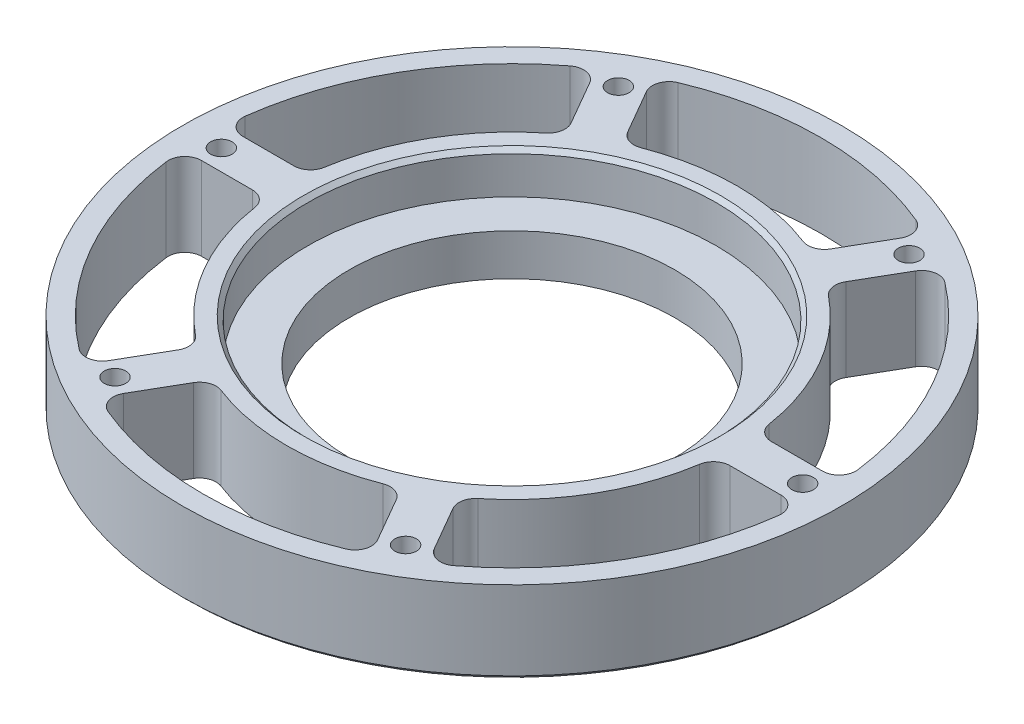
SolidWorks part; units mm, degrees
material "6061-T6 (SS)"
ref_plane "Front Plane" through (0, 0, 0) normal (0, 0, 1) x (1, 0, 0)
ref_plane "Top Plane" through (0, 0, 0) normal (0, 1, 0) x (1, 0, 0)
ref_plane "Right Plane" through (0, 0, 0) normal (1, 0, 0) x (0, 0, -1)
sketch "Sketch2" plane through (0, 0, 0) normal (1, 0, 0) x (0, 0, -1)
  line L0 (-39.2125, 0) -> (-79.375, 0)
  line L1 (-79.375, 0) -> (-79.375, 20)
  line L2 (-79.375, 20) -> (-49.2125, 20)
  line L3 (-49.2125, 20) -> (-49.2125, 10)
  line L4 (-49.2125, 10) -> (-39.2125, 10)
  line L5 (-39.2125, 10) -> (-39.2125, 0)
  dimension "D1" = 79.375
  dimension "D2" = 20
  dimension "D3" = 10
  dimension "D4" = 49.2125
  dimension "D5" = 10
ref_axis "Axis1" through (0, -1, 0) along (0, 1, 0)
revolve "Revolve1" add sketch "Sketch2" angle 360 about axis through (0, -1, 0) along (0, 1, 0)
hole_wizard "#6 (0.204) Diameter Hole1" positions "Sketch6" profile "Sketch7" hole size "#6" standard "ANSI Inch" end condition through all
sketch "Sketch6" plane through (0, 20, 0) normal (0, 1, 0) x (1, 0, 0)
  line L0 (0, 0) -> (-69.8201, 120.932) construction
  line L2 (0, 0) -> (0, 109.0908) construction
  point P0 (-35, 60.6218)
  dimension "D1" = 30
  dimension "D2" = 70
sketch "Sketch7" plane through (-35, 20, -60.6218) normal (1, 0, 0) x (0, 0, 1)
  line L0 (0, 0) -> (0, 20)
  line L1 (0, 20) -> (2.5908, 20)
  line L2 (2.5908, 20) -> (2.5908, 0)
  line L5 (2.5908, 0) -> (0, 0)
  line L11 (0, -6.35) -> (0, 107.95) construction
  dimension "Thru Hole Dia." = 5.1816
  dimension "Thru Hole Depth" = 20
pattern_circular "CirPattern3" count 6 over 360 about axis through (0, -1, 0) along (0, 1, 0) of "#6 (0.204) Diameter Hole1"
sketch "Sketch8" plane through (0, 20, 0) normal (0, 1, 0) x (1, 0, 0)
  line L0 (-32.7732, 66.7649) -> (-22.6606, 49.2493)
  line L1 (32.7732, 66.7649) -> (22.6606, 49.2493)
  line L2 (0, 0) -> (-35, 60.6218) construction
  line L4 (0, 0) -> (0, 93.9995) construction
  arc A0 (-22.6606, 49.2493) -> (22.6606, 49.2493) centre (0, 0) cw
  arc A1 (-32.7732, 66.7649) -> (32.7732, 66.7649) centre (0, 0) cw
  circle A2 centre (0, 0) radius 49.2125 construction
  circle A3 centre (0, 0) radius 79.375 construction
  dimension "D1" = 5
  dimension "D2" = 5
  dimension "D3" = 5
extrude "Cut-Extrude1" cut sketch "Sketch8" against normal through all
fillet "Fillet1" radius 4 4 edges at (32.7732, 10, -66.7649) (22.6606, 10, -49.2493) (-32.7732, 10, -66.7649) (-22.6606, 10, -49.2493)
pattern_circular "CirPattern4" count 6 over 360 about axis through (0, -1, 0) along (0, 1, 0) of "Cut-Extrude1", "Fillet1"
chamfer "Chamfer1" distance 1 angle 45 1 edges at (0, 20, -49.2125)
chamfer "Chamfer2" distance 1 angle 45 1 edges at (0, 0, -79.375)
equation "\"TubeDiameter\" = 6.250in"
equation "\"D1@Sketch2\"=\"TubeDiameter\"/2"
